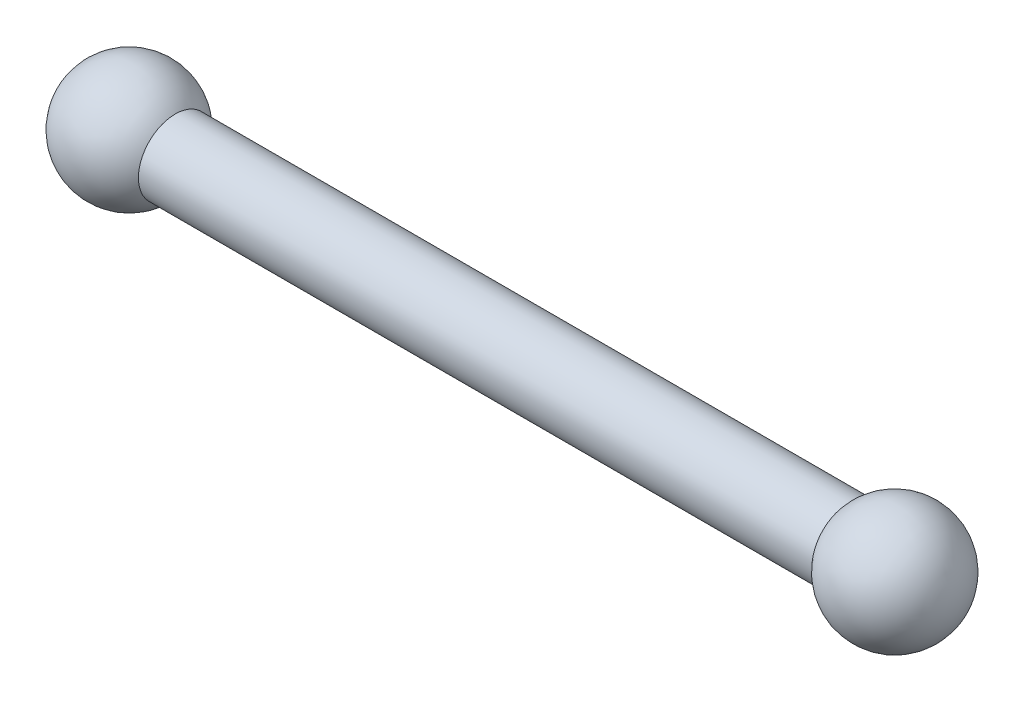
SolidWorks part; units mm, degrees
material "1060 Alloy"
ref_plane "Front Plane" through (0, 0, 0) normal (0, 0, 1) x (1, 0, 0)
ref_plane "Top Plane" through (0, 0, 0) normal (0, 1, 0) x (1, 0, 0)
ref_plane "Right Plane" through (0, 0, 0) normal (1, 0, 0) x (0, 0, -1)
sketch "Sketch1" plane through (0, 0, 0) normal (0, 0, 1) x (1, 0, 0)
  line L0 (0, 0) -> (0, 103.0383) construction
  line L1 (0, 0) -> (0, 12.7)
  line L2 (0, 12.7) -> (116.2177, 12.7)
  line L3 (0, 0) -> (152.4, 0)
  line L4 (0, 0) -> (399.4988, 0) construction
  arc A2 (116.2177, 12.7) -> (152.4, 0) centre (132.08, 0) cw
  dimension "D3" = 20.32
  dimension "D1" = 12.7
  dimension "D2" = 152.4
revolve "Revolve1" add sketch "Sketch1" angle 360 about L4
mirror "Mirror1" about plane through (0, 0, 0) normal (1, 0, 0) of "Revolve1"
sketch "Sketch2" plane through (0, 0, 0) normal (0, 0, 1) x (1, 0, 0)
  line L0 (0, 0) -> (0, 57.9452) construction
ref_axis "Axis1" through (0, 0, 0) along (0, 1, 0)
